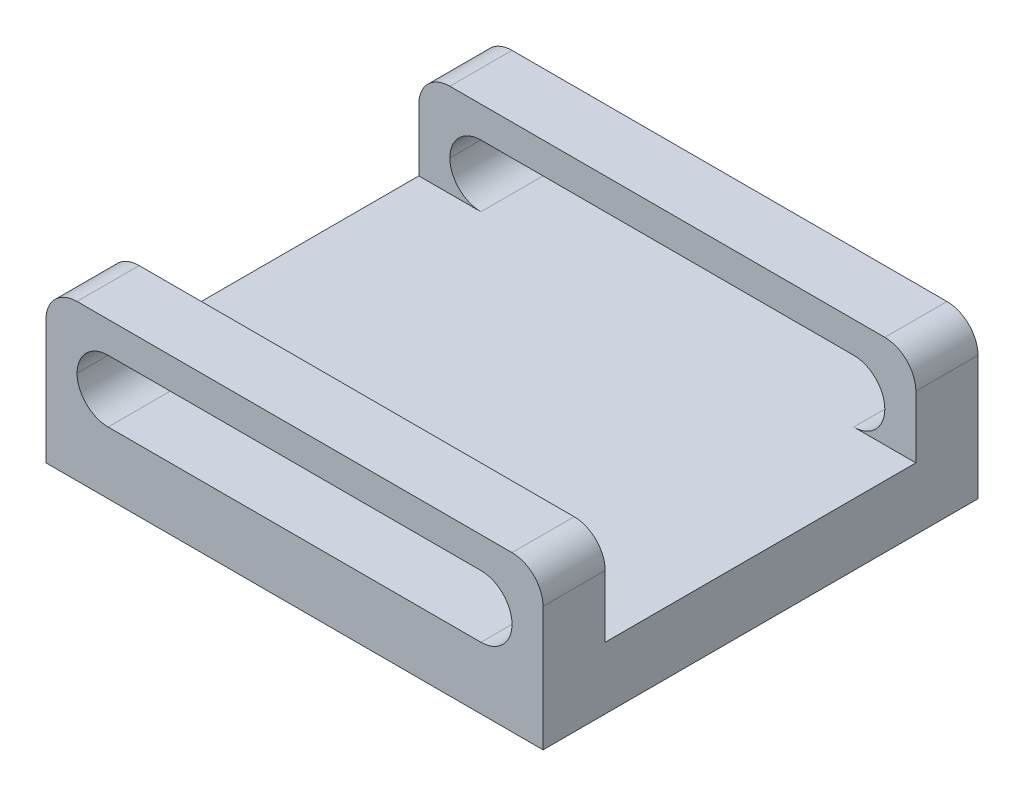
SolidWorks part; units mm, degrees
ref_plane "Front Plane" through (0, 0, 0) normal (0, 0, 1) x (1, 0, 0)
ref_plane "Top Plane" through (0, 0, 0) normal (0, 1, 0) x (1, 0, 0)
ref_plane "Right Plane" through (0, 0, 0) normal (1, 0, 0) x (0, 0, -1)
sketch "Sketch1" plane through (0, 0, 0) normal (0, 1, 0) x (1, 0, 0)
  line L1 (-8, -7) -> (8, -7)
  line L2 (-8, -7) -> (-8, 7)
  line L3 (-8, 7) -> (8, 7)
  line L4 (8, -7) -> (8, 7)
  line L5 (-8, -7) -> (8, 7) construction
  line L6 (-8, 7) -> (8, -7) construction
  point P0 (0, 0)
  dimension "D1" = 16
  dimension "D2" = 14
extrude "Boss-Extrude1" add sketch "Sketch1" along normal blind 2
sketch "Sketch3" plane through (0, 0, 7) normal (0, 0, 1) x (1, 0, 0)
  line L0 (-8, 2) -> (-8, 5)
  line L1 (-8, 5) -> (8, 5)
  line L2 (8, 5) -> (8, 2)
  line L3 (8, 2) -> (7, 2)
  line L4 (-8, 2) -> (8, 2) construction
  line L5 (7, 2) -> (7, 4)
  line L6 (7, 4) -> (-7, 4)
  line L7 (-7, 4) -> (-7, 2)
  line L8 (-7, 2) -> (-8, 2)
  dimension "D1" = 1
  dimension "D2" = 1
  dimension "D3" = 2
extrude "Boss-Extrude2" add sketch "Sketch3" against normal blind 2
fillet "Fillet1" radius 1 6 edges at (8, 5, 6) (-8, 5, 6) (-7, 4, 6) (-7, 2, 6) (7, 4, 6) (7, 2, 6)
mirror "Mirror1" about plane through (0, 0, 0) normal (0, 0, 1) of "Fillet1", "Boss-Extrude2"
